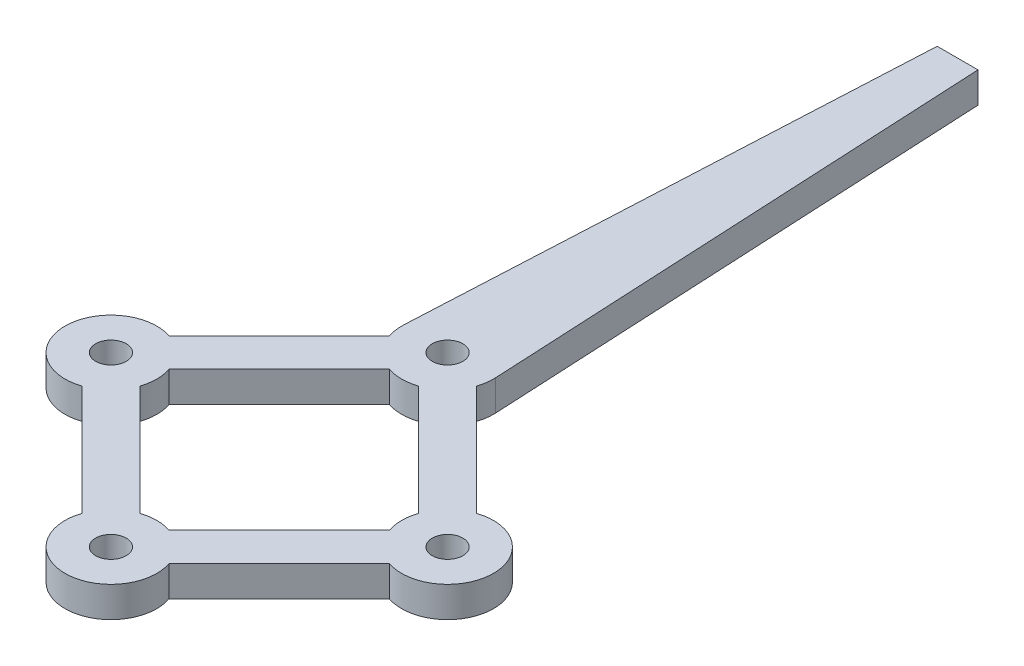
SolidWorks part; units mm, degrees
ref_plane "Front Plane" through (0, 0, 0) normal (0, 0, 1) x (1, 0, 0)
ref_plane "Top Plane" through (0, 0, 0) normal (0, 1, 0) x (1, 0, 0)
ref_plane "Right Plane" through (0, 0, 0) normal (1, 0, 0) x (0, 0, -1)
sketch "Sketch1" plane through (0, 0, 0) normal (0, 1, 0) x (1, 0, 0)
  line L0 (0, 0) -> (0, 83) construction
  line L1 (-2, 83) -> (2, 83)
  line L2 (2, 83) -> (4.4944, 33.2252)
  line L3 (0, 0) -> (16.5, 16.5) construction
  line L4 (16.5, 16.5) -> (0, 33) construction
  line L5 (-16.5, 16.5) -> (0, 0) construction
  line L6 (-16.5, 16.5) -> (0, 33) construction
  line L7 (-2, 83) -> (-4.4964, 33.1802)
  line L8 (15.0638, 20.7647) -> (4.2647, 31.5638)
  line L9 (-15.0638, 20.7647) -> (-4.2647, 31.5638)
  line L10 (-15.0638, 12.2353) -> (-4.2647, 1.4362)
  line L11 (4.2647, 1.4362) -> (15.0638, 12.2353)
  line L12 (12.2353, 17.9362) -> (1.4362, 28.7353)
  line L13 (-12.2353, 17.9362) -> (-1.4362, 28.7353)
  line L14 (-12.2353, 15.0638) -> (-1.4362, 4.2647)
  line L15 (1.4362, 4.2647) -> (12.2353, 15.0638)
  line L17 (-19.3284, 16.5) -> (0, -2.8284) construction
  line L18 (-19.3284, 16.5) -> (0, 35.8284) construction
  line L19 (19.3284, 16.5) -> (0, 35.8284) construction
  line L20 (0, -2.8284) -> (19.3284, 16.5) construction
  line L21 (-13.6716, 16.5) -> (0, 2.8284) construction
  line L22 (0, 2.8284) -> (13.6716, 16.5) construction
  line L23 (13.6716, 16.5) -> (0, 30.1716) construction
  line L24 (-13.6716, 16.5) -> (0, 30.1716) construction
  circle A0 centre (0, 0) radius 1.5
  circle A1 centre (0, 33) radius 1.5
  circle A2 centre (-16.5, 16.5) radius 1.5
  arc A3 (-12.2353, 15.0638) -> (-12.2353, 17.9362) centre (-16.5, 16.5) ccw
  circle A4 centre (16.5, 16.5) radius 1.5
  arc A5 (1.4362, 4.2647) -> (-1.4362, 4.2647) centre (0, 0) ccw
  arc A6 (12.2353, 17.9362) -> (12.2353, 15.0638) centre (16.5, 16.5) ccw
  arc A7 (-4.4964, 33.1802) -> (-4.2647, 31.5638) centre (0, 33) ccw
  arc A8 (-4.2647, 1.4362) -> (4.2647, 1.4362) centre (0, 0) ccw
  arc A9 (15.0638, 12.2353) -> (15.0638, 20.7647) centre (16.5, 16.5) ccw
  arc A10 (-15.0638, 20.7647) -> (-15.0638, 12.2353) centre (-16.5, 16.5) ccw
  arc A11 (4.2647, 31.5638) -> (4.4944, 33.2252) centre (0, 33) ccw
  arc A12 (-1.4362, 28.7353) -> (1.4362, 28.7353) centre (0, 33) ccw
  point P18 (18.6213, 16.5)
  point P19 (0, 35.1213)
  point P20 (-18.6213, 16.5)
  point P21 (0, -2.1213)
  point P22 (14.3787, 16.5)
  point P23 (0, 30.8787)
  point P24 (-14.3787, 16.5)
  point P25 (0, 2.1213)
  dimension "D1" = 3
  dimension "D2" = 9
  dimension "D3" = 2
  dimension "D4" = 16.5
  dimension "D5" = 16.5
  dimension "D6" = 4
  dimension "D7" = 50
  dimension "D8" = 2
extrude "Boss-Extrude1" add sketch "Sketch1" along normal blind 3
ref_axis "Axis1" through (0, 3, -33) along (0, -1, 0)
